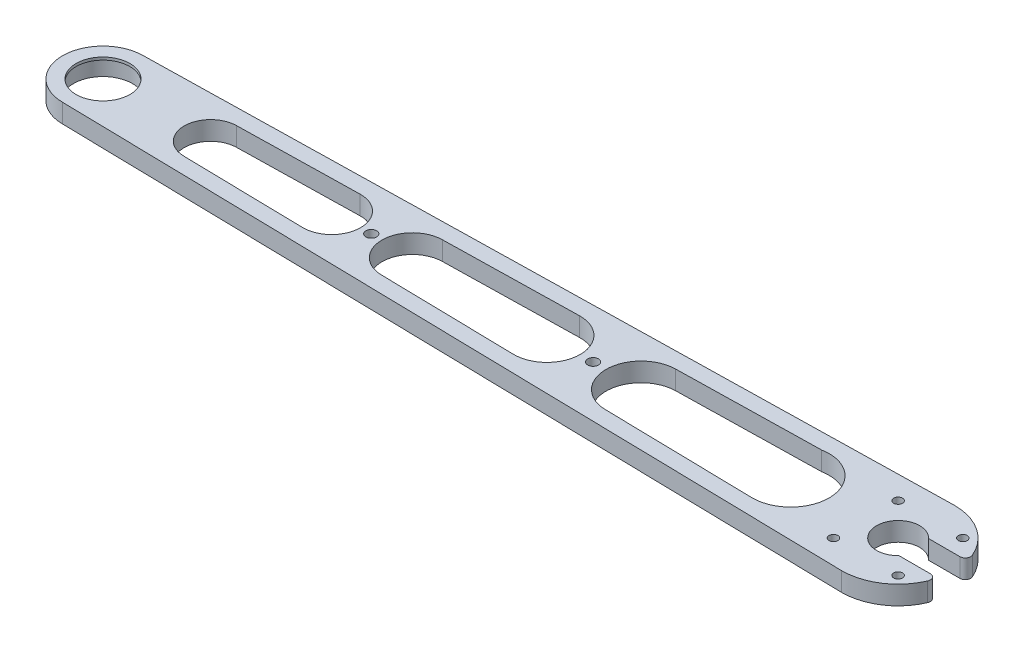
SolidWorks part; units mm, degrees
material "1060 Alloy"
ref_plane "Front Plane" through (0, 0, 0) normal (0, 0, 1) x (1, 0, 0)
ref_plane "Top Plane" through (0, 0, 0) normal (0, 1, 0) x (1, 0, 0)
ref_plane "Right Plane" through (0, 0, 0) normal (1, 0, 0) x (0, 0, -1)
sketch "Sketch1" plane through (0, 0, 0) normal (0, 1, 0) x (1, 0, 0)
  line L0 (-44.2539, 0) -> (44.2539, 0) construction
  line L1 (247.4804, -21) -> (-48.0196, -15)
  line L2 (-48.0196, 15) -> (247.4804, 21)
  line L3 (253.2898, 5.5) -> (264.9375, 5.5)
  line L4 (253.2898, -5.5) -> (264.9375, -5.5)
  arc A0 (-48.0196, 15) -> (-48.0196, -15) centre (-48.0196, 0) ccw
  arc A1 (246.6279, -20.9827) -> (266.775, -8.2895) centre (247.4804, 0) ccw
  arc A2 (253.2898, 5.5) -> (253.2898, -5.5) centre (247.4804, 0) ccw
  arc A3 (266.775, 8.2895) -> (246.6279, 20.9827) centre (247.4804, 0) ccw
  arc A4 (264.9375, 5.5) -> (266.775, 8.2895) centre (264.9375, 7.5) ccw
  arc A5 (264.9375, -5.5) -> (266.775, -8.2895) centre (264.9375, -7.5) cw
  circle A6 centre (-48.0196, 0) radius 10
  point P16 (267.7473, 5.5)
  dimension "D1" = 42
  dimension "D2" = 30
  dimension "D4" = 16
  dimension "D7" = 2
  dimension "D3" = 295.5
  dimension "D5" = 11
  dimension "D6" = 5.5
extrude "Boss-Extrude1" add sketch "Sketch1" along normal blind 7 contours A5 L4 A2 L3 A4 A3 L2 A0 L1 A1 A6 region at (111.8502, 0, 0)
ref_axis "Axis1" through (247.4804, 52.1339, 0) along (0, -1, 0)
ref_plane "Plane1" through (123.7402, 0, 123.7402) normal (0.7071, 0, 0.7071) x (0, -1, 0)
hole_wizard "Tap Drill for M4 Tap1" positions "Sketch2" profile "Sketch3" hole size "M4" standard "ISO"
sketch "Sketch2" plane through (0, 7, 0) normal (0, 1, 0) x (1, 0, 0)
  line L0 (96.347, -151.1333) -> (151.1333, -96.347) construction
  point P0 (259.5012, 12.0208)
  dimension "D1" = 17
sketch "Sketch3" plane through (259.5012, 7, -12.0208) normal (1, 0, 0) x (0, 0, 1)
  line L0 (0, 0) -> (0, 8.9914)
  line L1 (0, 8.9914) -> (1.65, 8)
  line L2 (1.65, 8) -> (1.65, 0)
  line L5 (1.65, 0) -> (0, 0)
  line L10 (0, 8.9914) -> (-1.65, 8) construction
  line L11 (0, -6.35) -> (0, 107.95) construction
  dimension "Hole Dia." = 3.3
  dimension "Hole Depth" = 8
  dimension "Drill Angle" = 118
pattern_circular "CirPattern1" count 4 over 360 about axis through (247.4804, 52.1339, 0) along (0, -1, 0) of "Tap Drill for M4 Tap1"
sketch "Sketch4" plane through (0, 0, 0) normal (0, 1, 0) x (1, 0, 0)
  circle A0 centre (-48.0196, 0) radius 11
extrude "Cut-Extrude2" cut sketch "Sketch4" along normal blind 6
hole_wizard "M4 Tapped Hole1" positions "Sketch5" profile "Sketch6" tap size "M4" standard "ISO"
sketch "Sketch5" plane through (0, 0, 0) normal (0, -1, 0) x (-1, 0, 0)
  line L0 (-44.2539, 0) -> (44.2539, 0) construction
  circle A0 centre (48.0196, 0) radius 11 construction
  point P0 (33.0196, -10)
  point P2 (33.0196, 10)
  dimension "D1" = 15
  dimension "D2" = 0
  dimension "D3" = 10
  dimension "D4" = 10
sketch "Sketch6" plane through (-33.0196, 0, 10) normal (1, 0, 0) x (0, 0, -1)
  line L0 (0, 0) -> (0, 5.9914)
  line L1 (0, 5.9914) -> (1.65, 5)
  line L2 (1.65, 5) -> (1.65, 0)
  line L5 (1.65, 0) -> (0, 0)
  line L10 (0, 5.9914) -> (-1.65, 5) construction
  line L11 (0, -6.35) -> (0, 107.95) construction
  dimension "Tap Drill Dia." = 3.3
  dimension "Tap Drill Depth" = 5
  dimension "Drill Angle" = 118
cosmetic thread "Hole Thread1" parameters "D1"=5, "D2"=4
cosmetic thread "Hole Thread2" parameters "D1"=5, "D2"=4
sketch "Sketch7" plane through (0, 0, 0) normal (0, -1, 0) x (-1, 0, 0)
  line L0 (8.2188, -9.8069) -> (-36.7627, -10.7202)
  line L1 (8.2188, 9.8069) -> (-36.7627, 10.7202)
  line L2 (-247.4804, -21) -> (48.0196, -15) construction
  line L3 (48.0196, 15) -> (-247.4804, 21) construction
  line L4 (-44.2539, 0) -> (44.2539, 0) construction
  line L5 (-66.7503, 11.3291) -> (-116.7297, 12.3439)
  line L6 (-66.7503, -11.3291) -> (-116.7297, -12.3439)
  line L7 (-151.7153, -13.0543) -> (-207.1907, -14.1807)
  line L8 (-151.7153, 13.0543) -> (-204.9183, 14.1346)
  line L9 (-138.9234, 0) -> (-129.3268, 0) construction
  line L10 (-55.6489, 0) -> (-47.7028, 0) construction
  arc A0 (8.2188, -9.8069) -> (8.2188, 9.8069) centre (8.0196, 0) ccw
  arc A1 (-207.1907, -14.1807) -> (-204.9183, 14.1346) centre (-207.4805, 0.0914) cw
  arc A2 (-36.7627, -10.7202) -> (-36.7627, 10.7202) centre (-36.9804, 0) cw
  arc A3 (-66.7503, 11.3291) -> (-66.7503, -11.3291) centre (-66.9804, 0) cw
  circle A4 centre (48.0196, 0) radius 10 construction
  arc A5 (-116.7297, 12.3439) -> (-116.7297, -12.3439) centre (-116.9804, 0) ccw
  arc A6 (-151.7153, 13.0543) -> (-151.7153, -13.0543) centre (-151.9804, 0) cw
  circle A7 centre (-134.1251, 0) radius 2
  circle A8 centre (-51.6759, 0) radius 2
  point P37 (-51.6759, 0)
  point P39 (-134.1251, 0)
  dimension "D9" = 4
  dimension "D1" = 6
  dimension "D2" = 6
  dimension "D4" = 40
  dimension "D3" = 40
  dimension "D5" = 30
  dimension "D6" = 45
  dimension "D7" = 35
  dimension "D8" = 50
extrude "Cut-Extrude3" cut sketch "Sketch7" against normal blind 7
ref_plane "Plane2" through (0, 3.5, 0) normal (0, 1, 0) x (1, 0, 0)
equation "\"wallthickness\"=6"
equation "\"D1@Sketch7\"=\"wallthickness\""
equation "\"D2@Sketch7\"=\"wallthickness\""
